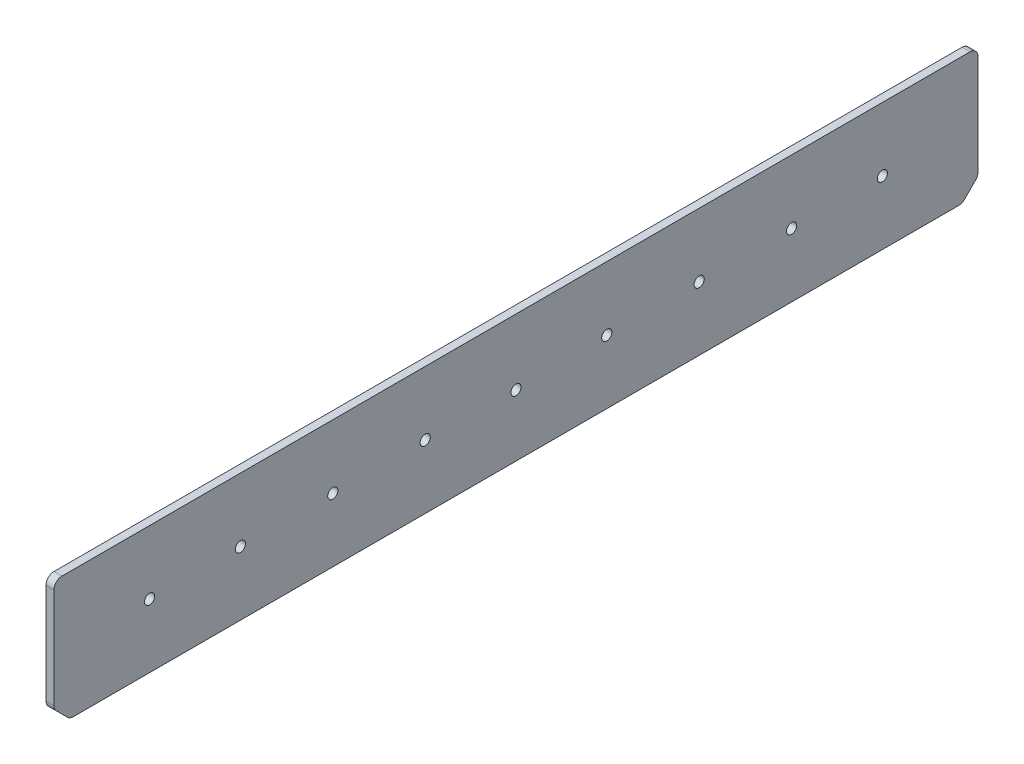
SolidWorks part; units mm, degrees
ref_plane "Front Plane" through (0, 0, 0) normal (0, 0, 1) x (1, 0, 0)
ref_plane "Top Plane" through (0, 0, 0) normal (0, 1, 0) x (1, 0, 0)
ref_plane "Right Plane" through (0, 0, 0) normal (1, 0, 0) x (0, 0, -1)
sketch "Sketch1" plane through (0, 0, 0) normal (1, 0, 0) x (0, 0, -1)
  line L1 (0, 0) -> (368.3, 0)
  line L2 (0, 0) -> (0, 50.8)
  line L3 (0, 50.8) -> (368.3, 50.8)
  line L4 (368.3, 0) -> (368.3, 50.8)
  dimension "D1" = 50.8
  dimension "D2" = 368.3
extrude "Boss-Extrude1" add sketch "Sketch1" along normal blind 3.175
sketch "Sketch2" plane through (3.175, 0, 0) normal (1, 0, 0) x (0, 0, -1)
  circle A18 centre (330.1913, 25.4) radius 2.032 construction
  circle A19 centre (184.15, 24.6063) radius 2.032 construction
  circle A20 centre (111.1337, 25.4) radius 2.032 construction
  circle A21 centre (74.3037, 25.4) radius 2.032 construction
  circle A22 centre (38.1087, 25.4) radius 2.032 construction
  circle A23 centre (330.1913, 25.4) radius 2.032
  circle A24 centre (184.15, 24.6063) radius 2.032
  circle A25 centre (111.1337, 25.4) radius 2.032
  circle A26 centre (74.3037, 25.4) radius 2.032
  circle A27 centre (38.1087, 25.4) radius 2.032
  circle A28 centre (147.9637, 25.4) radius 2.032
  circle A29 centre (220.3363, 25.4) radius 2.032
  circle A30 centre (257.1663, 25.4) radius 2.032
  circle A31 centre (293.9963, 25.4) radius 2.032
  circle A32 centre (147.9637, 25.4) radius 4.7625 construction
  circle A33 centre (220.3363, 25.4) radius 4.7625 construction
  circle A34 centre (257.1663, 25.4) radius 4.7625 construction
  circle A35 centre (293.9963, 25.4) radius 4.7625 construction
extrude "Cut-Extrude1" cut sketch "Sketch2" against normal through all
chamfer "Chamfer1" distance 6.35 angle 45 2 edges at (1.5875, 0, 0) (1.5875, 0, -368.3)
fillet "Fillet1" radius 3.175 6 edges at (1.5875, 0, -361.95) (1.5875, 6.35, -368.3) (1.5875, 50.8, -368.3) (1.5875, 0, -6.35) (1.5875, 6.35, 0) (1.5875, 50.8, 0)
